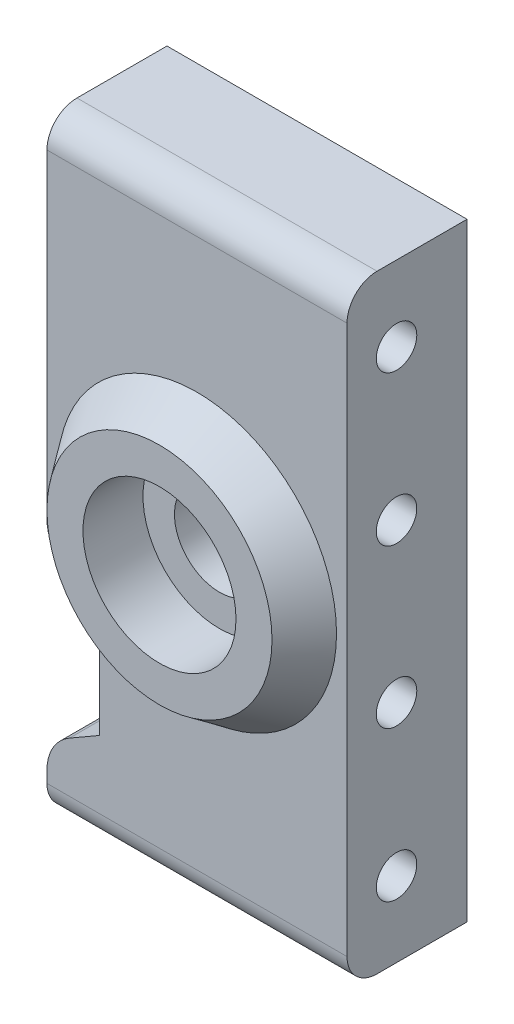
SolidWorks part; units mm, degrees
ref_plane "Front Plane" through (0, 0, 0) normal (0, 0, 1) x (1, 0, 0)
ref_plane "Top Plane" through (0, 0, 0) normal (0, 1, 0) x (1, 0, 0)
ref_plane "Right Plane" through (0, 0, 0) normal (1, 0, 0) x (0, 0, -1)
sketch "Sketch1" plane through (0, 0, 0) normal (0, 0, 1) x (1, 0, 0)
  line L0 (-10, 20.2804) -> (-10, -20.2804)
  line L1 (-10, -20.2804) -> (10, -20.2804)
  line L2 (10, -20.2804) -> (10, 20.2804)
  line L3 (10, 20.2804) -> (-10, 20.2804)
  line L4 (-10, 20.2804) -> (10, -20.2804) construction
  line L11 (-10, -20.2804) -> (10, 20.2804) construction
  point P9 (0, 0)
  dimension "D1" = 20
  dimension "D2" = 40.5608
extrude "Boss-Extrude1" add sketch "Sketch1" against normal blind 8
sketch "Sketch6" plane through (10, 0, 0) normal (1, 0, 0) x (0, 0, -1)
  line L0 (0, -20.2804) -> (0, 20.2804) construction
  line L1 (3.3, -5.2652) -> (3.3, -15.2652) construction
  line L2 (3.3, 4.95) -> (3.3, 15.6283) construction
  line L3 (0, 0) -> (8, 0) construction
  line L4 (8, -20.2804) -> (8, 20.2804) construction
  line L5 (23.2424, -10.2652) -> (-16.6424, -10.2652) construction
  line L6 (8, -20.2804) -> (0, -20.2804) construction
  line L7 (23.2424, -0.25) -> (-16.6424, -0.25) construction
  circle A0 centre (3.3, -15.2652) radius 1.35
  circle A1 centre (3.3, -5.2652) radius 1.35
  circle A2 centre (3.3, 15.2652) radius 1.35
  circle A3 centre (3.3, 5.2652) radius 1.35
  point P15 (3.3, -10.2652)
  dimension "D1" = 2.7
  dimension "D2" = 4.7
  dimension "D3" = 10.0152
  dimension "D4" = 10
  dimension "D5" = 10.0152
extrude "Cut-Extrude1" cut sketch "Sketch6" against normal blind 10
sketch "Sketch8" plane through (0, 0, 0) normal (0, 0, 1) x (1, 0, 0)
  line L0 (-10, 20.2804) -> (10, -20.2804) construction
  circle A0 centre (0, 0) radius 7.5
  dimension "D1" = 15
extrude "Boss-Extrude2" add sketch "Sketch8" along normal blind 2.5
sketch "Sketch9" plane through (0, 0, 2.5) normal (0, 0, 1) x (1, 0, 0)
  circle A0 centre (0, 0) radius 5.1
  dimension "D1" = 10.2
extrude "Cut-Extrude3" cut sketch "Sketch9" against normal blind 4
sketch "Sketch10" plane through (0, 0, -1.5) normal (0, 0, 1) x (1, 0, 0)
  circle A0 centre (0, 0) radius 3
  dimension "D1" = 6
extrude "Cut-Extrude4" cut sketch "Sketch10" against normal up to surface (6.5 mm away) up to face at (0, 0, -8)
fillet "Fillet1" radius 2 2 edges at (0, -20.2804, 0) (0, 20.2804, 0) tangent propagation no
chamfer "Chamfer1" distance 1.8 distance2 2.5 1 edges at (7.5, 0, 0) first distance on face at (7.5, 0, 0)
sketch "Sketch11" plane through (-10, 0, 0) normal (-1, 0, 0) x (0, 0, 1)
  line L0 (-8, -10.2652) -> (0, -10.2652) construction
  line L1 (-8, 20.2804) -> (-8, -20.2804) construction
  line L2 (0, 18.2804) -> (0, -18.2804) construction
  line L3 (-8, -20.2804) -> (-2, -20.2804) construction
  line L4 (-8, -13.7652) -> (0, -13.7652)
  line L5 (-8, -6.7652) -> (0, -6.7652)
  line L6 (0, -6.7652) -> (0, -13.7652)
  line L7 (-8, -13.7652) -> (-8, -6.7652)
  dimension "D1" = 10.0152
  dimension "D2" = 3.5
  dimension "D3" = 3.5
extrude "Cut-Extrude5" cut sketch "Sketch11" against normal blind 3.5
chamfer "Chamfer2" distance 3.5 angle 30 2 edges at (-10, -13.7652, -4) (-10, -6.7652, -4) first distance on face at (-8.25, -13.7652, -4) first distance on face at (-8.25, -6.7652, -4)
fillet "Fillet2" radius 3 2 edges at (-10, -15.7859, -4) (-10, -4.7444, -4)
